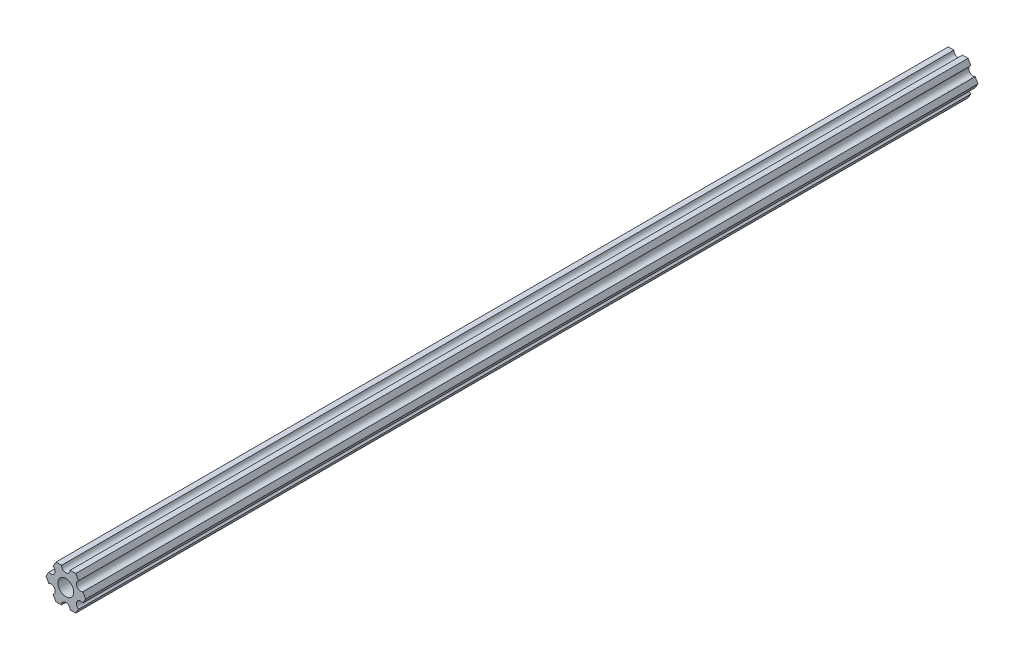
SolidWorks part; units mm, degrees
material "6061-T6 (SS)"
ref_plane "Front Plane" through (0, 0, 0) normal (0, 0, 1) x (1, 0, 0)
ref_plane "Top Plane" through (0, 0, 0) normal (0, 1, 0) x (1, 0, 0)
ref_plane "Right Plane" through (0, 0, 0) normal (1, 0, 0) x (0, 0, -1)
sketch "Sketch1" plane through (0, 0, 0) normal (0, 0, 1) x (1, 0, 0)
  line L0 (-4.7055, -4.5498) -> (-3.6662, -6.35)
  line L1 (-3.6662, -6.35) -> (-1.5875, -6.35)
  line L2 (1.5875, -6.35) -> (3.6662, -6.35)
  line L3 (3.6662, -6.35) -> (4.7055, -4.5498)
  line L4 (6.293, -1.8002) -> (7.3323, 0)
  line L5 (7.3323, 0) -> (6.293, 1.8002)
  line L6 (4.7055, 4.5498) -> (3.6662, 6.35)
  line L7 (3.6662, 6.35) -> (1.5875, 6.35)
  line L8 (-1.5875, 6.35) -> (-3.6662, 6.35)
  line L9 (-3.6662, 6.35) -> (-4.7055, 4.5498)
  line L10 (-6.293, 1.8002) -> (-7.3323, 0)
  line L11 (-7.3323, 0) -> (-6.293, -1.8002)
  circle A0 centre (0, 0) radius 2.9337
  arc A1 (-6.293, -1.8002) -> (-4.7055, -4.5498) centre (-5.4993, -3.175) cw
  arc A2 (-1.5875, -6.35) -> (1.5875, -6.35) centre (0, -6.35) cw
  arc A3 (4.7055, -4.5498) -> (6.293, -1.8002) centre (5.4993, -3.175) cw
  arc A4 (6.293, 1.8002) -> (4.7055, 4.5498) centre (5.4993, 3.175) cw
  arc A5 (1.5875, 6.35) -> (-1.5875, 6.35) centre (0, 6.35) cw
  arc A6 (-4.7055, 4.5498) -> (-6.293, 1.8002) centre (-5.4993, 3.175) cw
extrude "Boss-Extrude1" add sketch "Sketch1" against normal blind 330.2
